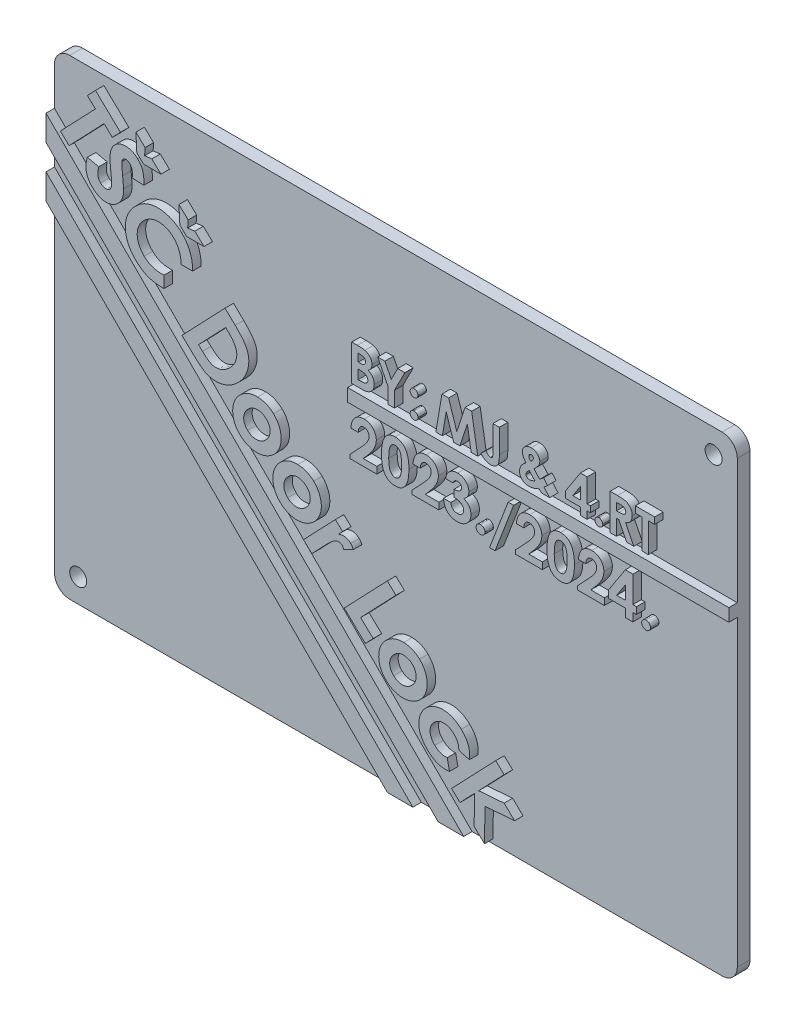
SolidWorks part; units mm, degrees
ref_plane "Front Plane" through (0, 0, 0) normal (0, 0, 1) x (1, 0, 0)
ref_plane "Top Plane" through (0, 0, 0) normal (0, 1, 0) x (1, 0, 0)
ref_plane "Right Plane" through (0, 0, 0) normal (1, 0, 0) x (0, 0, -1)
sketch "Sketch1" plane through (0, 0, 0) normal (0, 0, 1) x (1, 0, 0)
  line L0 (-6.2162, 53.4731) -> (70.7838, 53.4731) construction
  line L1 (-8.2162, 51.4731) -> (-8.2162, -0.5269) construction
  line L2 (-6.2162, -2.5269) -> (70.7838, -2.5269) construction
  line L3 (72.7838, 51.4731) -> (72.7838, -0.5269) construction
  line L4 (-6.2162, 53.2731) -> (70.7838, 53.2731)
  line L5 (72.5838, 51.4731) -> (72.5838, -0.5269)
  line L6 (-6.2162, -2.3269) -> (70.7838, -2.3269)
  line L7 (-8.0162, 51.4731) -> (-8.0162, -0.5269)
  arc A0 (70.7838, 53.4731) -> (72.7838, 51.4731) centre (70.7838, 51.4731) cw construction
  arc A1 (70.7838, -2.5269) -> (72.7838, -0.5269) centre (70.7838, -0.5269) ccw construction
  arc A2 (-8.2162, -0.5269) -> (-6.2162, -2.5269) centre (-6.2162, -0.5269) ccw construction
  arc A3 (-6.2162, 53.4731) -> (-8.2162, 51.4731) centre (-6.2162, 51.4731) ccw construction
  circle A4 centre (-5.2162, 0.4731) radius 1
  circle A5 centre (69.7838, 50.4731) radius 1
  arc A6 (70.7838, 53.2731) -> (72.5838, 51.4731) centre (70.7838, 51.4731) cw
  arc A7 (70.7838, -2.3269) -> (72.5838, -0.5269) centre (70.7838, -0.5269) ccw
  arc A8 (-8.0162, -0.5269) -> (-6.2162, -2.3269) centre (-6.2162, -0.5269) ccw
  arc A9 (-6.2162, 53.2731) -> (-8.0162, 51.4731) centre (-6.2162, 51.4731) ccw
  dimension "D1" = 2
  dimension "D2" = 0.2
extrude "Boss-Extrude1" add sketch "Sketch1" along normal blind 1.5
sketch "Sketch2" plane through (0, 0, 1.5) normal (0, 0, 1) x (1, 0, 0)
  line L0 (-8.0162, 37.9731) -> (32.2838, -2.3269)
  line L1 (-8.0162, 51.4731) -> (-8.0162, -0.5269) construction
  line L2 (-6.2162, -2.3269) -> (70.7838, -2.3269) construction
  line L3 (32.2838, -2.3269) -> (35.2838, -2.3269)
  line L4 (35.2838, -2.3269) -> (-8.0162, 40.9731)
  line L5 (-8.0162, 40.9731) -> (-8.0162, 37.9731)
  line L6 (-8.0162, 43.9731) -> (38.2838, -2.3269)
  line L7 (38.2838, -2.3269) -> (41.2838, -2.3269)
  line L8 (41.2838, -2.3269) -> (-8.0162, 46.9731)
  line L9 (-8.0162, 46.9731) -> (-8.0162, 43.9731)
  dimension "D1" = 3
  dimension "D2" = 3
  dimension "D3" = 3
  dimension "D4" = 3
  dimension "D5" = 3
  dimension "D6" = 3
extrude "Boss-Extrude2" add sketch "Sketch2" along normal blind 1
sketch "Sketch3" plane through (0, 0, 1.5) normal (0, 0, 1) x (1, 0, 0)
  line L0 (-7.3457, 46.9731) -> (42.3942, -0.5494) construction
  text T0 "<b>TŠČ Door Lock</b>" font "Century Gothic" height in points 28
extrude "Boss-Extrude3" add sketch "Sketch3" along normal blind 1
sketch "Sketch4" plane through (0, 0, 1.5) normal (0, 0, 1) x (1, 0, 0)
  line L0 (72.5838, -0.5269) -> (72.5838, 51.4731) construction
  line L1 (27.5838, 35.2241) -> (72.5838, 35.2241)
  line L2 (27.5838, 35.2241) -> (27.5838, 36.7241)
  line L3 (27.5838, 36.7241) -> (72.5838, 36.7241)
  line L4 (72.5838, 35.2241) -> (72.5838, 36.7241)
  line L5 (27.5838, 37.3846) -> (72.5838, 37.3846) construction
  text T0 "<b>BY: MJ & 4.RT</b>" font "Century Gothic" height in points 16
  dimension "D1" = 45
  dimension "D2" = 1.5
extrude "Boss-Extrude4" add sketch "Sketch4" along normal blind 1
sketch "Sketch5" plane through (0, 0, 1.5) normal (0, 0, 1) x (1, 0, 0)
  line L0 (27.7352, 29.5952) -> (72.5838, 29.5952) construction
  line L1 (72.5838, -0.5269) -> (72.5838, 35.2241) construction
  text T0 "<b>2023./2024.</b>" font "Century Gothic" height in points 18
extrude "Boss-Extrude5" add sketch "Sketch5" along normal blind 1
